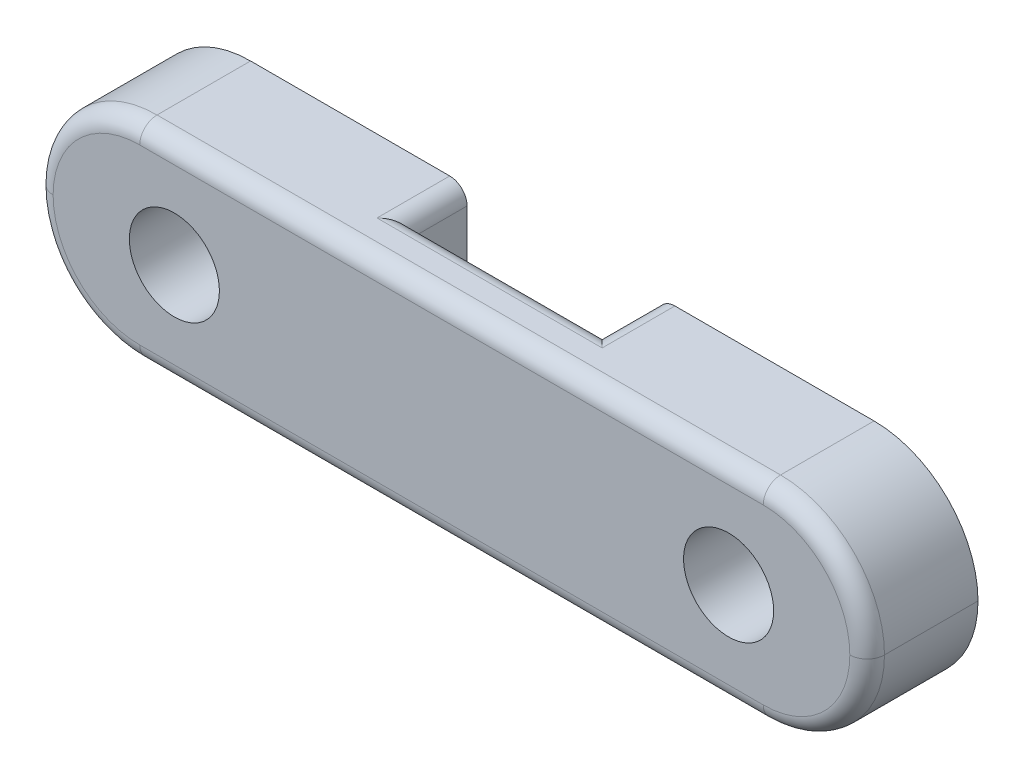
SolidWorks part; units mm, degrees
ref_plane "Front Plane" through (0, 0, 0) normal (0, 0, 1) x (1, 0, 0)
ref_plane "Top Plane" through (0, 0, 0) normal (0, 1, 0) x (1, 0, 0)
ref_plane "Right Plane" through (0, 0, 0) normal (1, 0, 0) x (0, 0, -1)
sketch "Sketch1" plane through (0, 0, 0) normal (0, 0, 1) x (1, 0, 0)
  line L0 (-12, 0) -> (12, 0) construction
  line L1 (-12, -3) -> (12, -3)
  line L2 (-12, -3) -> (-12, 3)
  line L3 (-12, 3) -> (12, 3)
  line L4 (12, -3) -> (12, 3)
  line L5 (-12, -3) -> (12, 3) construction
  line L6 (-12, 3) -> (12, -3) construction
  line L7 (-8, 0) -> (0, 3) construction
  line L8 (0, 3) -> (8, 0) construction
  circle A0 centre (-8, 0) radius 1.3
  circle A1 centre (8, 0) radius 1.3
  point P0 (0, 0)
  dimension "D1" = 2.6
  dimension "D2" = 16
  dimension "D3" = 24
  dimension "D4" = 6
extrude "Boss-Extrude1" add sketch "Sketch1" along normal blind 3.2
sketch "Sketch2" plane through (0, 0, 0) normal (0, 0, -1) x (-1, 0, 0)
  line L0 (-12, 3) -> (12, 3) construction
  line L1 (-2.75, -3) -> (2.75, -3)
  line L2 (-2.75, -3) -> (-2.75, 3)
  line L3 (-2.75, 3) -> (2.75, 3)
  line L4 (2.75, -3) -> (2.75, 3)
  line L5 (-2.75, -3) -> (2.75, 3) construction
  line L6 (-2.75, 3) -> (2.75, -3) construction
  point P0 (0, 0)
  dimension "D1" = 5.5
extrude "Cut-Extrude1" cut sketch "Sketch2" against normal blind 1.6
fillet "Fillet1" radius 3 4 edges at (-12, -3, 1.6) (-12, 3, 1.6) (12, -3, 1.6) (12, 3, 1.6)
fillet "Fillet2" radius 0.5 12 edges at (11.1213, 2.1213, 3.2) (11.1213, -2.1213, 3.2) (0, -3, 3.2) (-11.1213, -2.1213, 3.2) (-11.1213, 2.1213, 3.2) (0, 3, 3.2) (2.75, -3, 0.8) (0, -3, 1.6) (-2.75, -3, 0.8) (2.75, 3, 0.8) (-2.75, 3, 0.8) (0, 3, 1.6)
